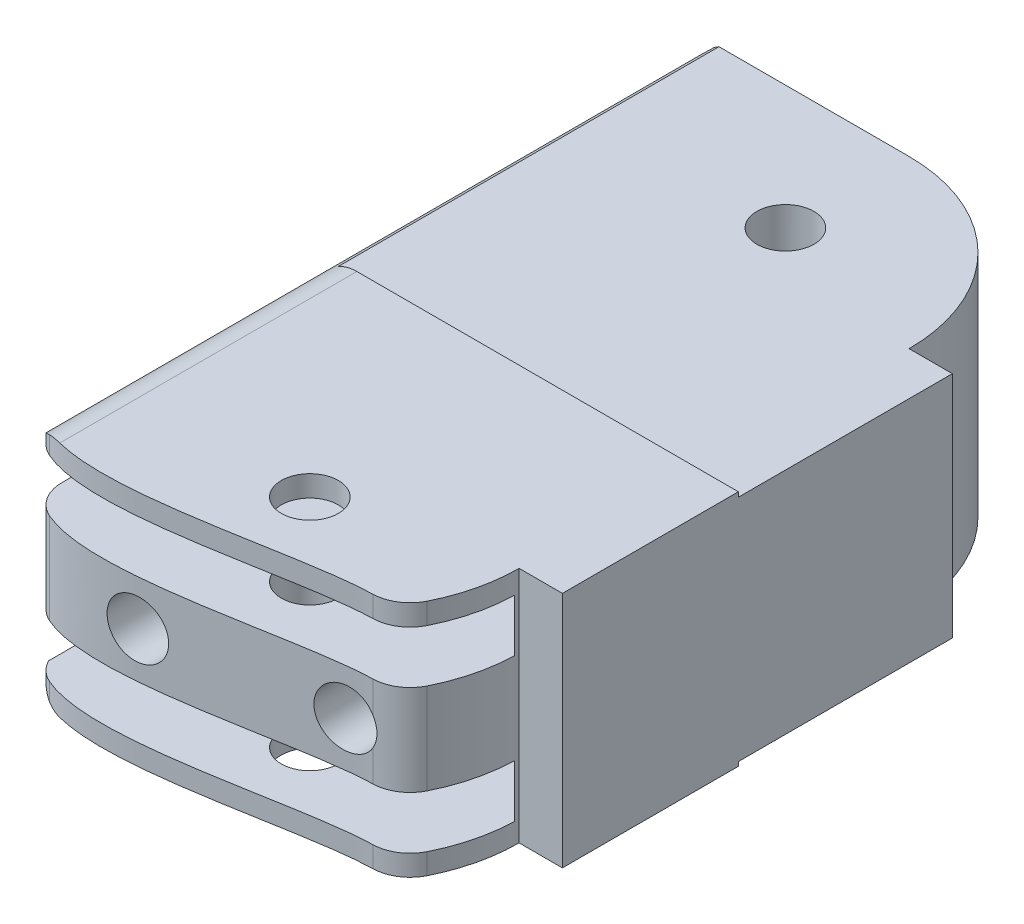
SolidWorks part; units mm, degrees
ref_plane "Front Plane" through (0, 0, 0) normal (0, 0, 1) x (1, 0, 0)
ref_plane "Top Plane" through (0, 0, 0) normal (0, 1, 0) x (1, 0, 0)
ref_plane "Right Plane" through (0, 0, 0) normal (1, 0, 0) x (0, 0, -1)
sketch "Sketch1" plane through (0, 0, 0) normal (0, 0, 1) x (1, 0, 0)
  line L0 (-24.2561, -24.0702) -> (-22.0061, -24.0702) construction
  line L1 (-24.2561, -17.8202) -> (-2.2017, -17.8202)
  line L2 (-24.2561, -17.8202) -> (-24.2561, -30.3202)
  line L3 (-24.2561, -30.3202) -> (-2.2017, -30.3202)
  line L4 (-2.2017, -17.8202) -> (-2.2017, -30.3202)
  line L5 (-2.2017, -24.0702) -> (-4.4517, -24.0702) construction
  line L6 (-22.0061, -24.0702) -> (-22.0061, -30.3202) construction
  line L7 (-4.4517, -24.0702) -> (-4.4517, -30.3202) construction
extrude "Boss-Extrude1" add sketch "Sketch1" along normal blind 38
sketch "Sketch2" plane through (0, -30.3202, 0) normal (0, -1, 0) x (1, 0, 0)
  line L0 (-4.4789, 29.25) -> (-2.2017, 29.25)
  line L1 (-24.2561, 0) -> (-2.2017, 0) construction
  line L2 (-13.2289, 0) -> (-13.2289, 8.75) construction
  line L4 (-24.2561, 38) -> (-24.2561, 0) construction
  line L5 (-4.4789, 8.75) -> (-2.2017, 8.75)
  line L6 (-2.2017, 38) -> (-2.2017, 0) construction
  line L7 (-13.2289, 38) -> (-13.2289, 29.25) construction
  line L8 (-24.2561, 38) -> (-2.2017, 38) construction
  line L10 (-13.2289, 29.25) -> (-13.2289, 31.5) construction
  line L11 (-13.2289, 8.75) -> (-13.2289, 6.5) construction
  line L12 (-24.2561, 0) -> (-2.2017, 0) construction
  arc A1 (-13.2289, 0) -> (-4.4789, 8.75) centre (-13.2289, 8.75) ccw
  circle A4 centre (-13.2289, 6.5) radius 1.5
  circle A5 centre (-13.2289, 31.5) radius 1.5
  arc A6 (-4.4789, 29.25) -> (-6.1039, 34.329) centre (-13.2289, 29.25) ccw
  spline S0 degree 3 poles (-2.2017, 8.75) (5.3921, 3.8803) (-0.7771, -4.5233) (-17.1743, -10.6233) (-34.8214, -0.026) (-24.2561, 8.75) knots 0 0 0 0 0.283273 0.504245 1 1 1 1
  spline S1 degree 3 poles (-24.2561, 29.25) (-34.2779, 38.4171) (-13.2275, 50.308) (7.8404, 38.417) (-2.2017, 29.25) knots 0 0 0 0 0.499862 1 1 1 1
  spline S2 degree 1 poles (-13.2289, 0) (-23.4906, 0) knots 0 0 1 1
  spline S3 degree 2 poles (-23.4906, 0) (-24.9665, 4.2378) (-24.2561, 8.75) knots 0 0 0 1 1 1
  spline S4 degree 3 poles (-6.1039, 34.329) (-10.7206, 33.5272) (-28.6414, 40.8452) (-24.2561, 29.25) knots 0 0 0 0 1 1 1 1
extrude "Cut-Extrude1" cut sketch "Sketch2" against normal blind 15 and the other way blind 10
fillet "Fillet3" radius 2 4 edges at (-24.2561, -17.8202, 18.7439) (-24.2561, -30.3202, 18.7439) (-24.2561, -24.0702, 3.0015) (-24.2561, -24.0702, 34.4864)
ref_plane "Plane1" through (0, 0, 0) normal (0, 0, 1) x (1, 0, 0)
sketch "Sketch5" plane through (0, 0, 0) normal (0, 0, 1) x (1, 0, 0)
  line L0 (-2.2017, -24.0702) -> (-8.4468, -24.0702) construction
  line L1 (-2.2017, -30.3202) -> (-24.2561, -30.3202) construction
  line L2 (-2.2017, -30.3202) -> (-2.2017, -17.8202) construction
  line L3 (-2.2017, -17.8202) -> (-24.2561, -17.8202) construction
  line L4 (-24.2561, -30.3202) -> (-24.2561, -17.8202) construction
  line L5 (-24.2561, -24.0702) -> (-18.0111, -24.0702) construction
  circle A0 centre (-18.0111, -24.0702) radius 1.5
  circle A1 centre (-8.4468, -24.0702) radius 1.5
extrude "Cut-Extrude4" cut sketch "Sketch5" along normal through all
ref_plane "Plane5" through (0, 0, 38) normal (0, 0, 1) x (1, 0, 0)
sketch "Sketch16" plane through (0, 0, 38) normal (0, 0, 1) x (1, 0, 0)
  line L0 (-2.2017, -17.681) -> (-2.2017, -18.9317) construction
  line L1 (-2.2017, -17.681) -> (-24.2561, -17.681) construction
  line L3 (-2.2017, -30.7619) -> (-24.2561, -30.7619) construction
  line L5 (-2.2017, -17.681) -> (-24.2561, -30.7619) construction
  line L6 (-2.2017, -30.7619) -> (-24.2561, -17.681) construction
  line L7 (-8.4468, -24.0702) -> (-8.4468, -26.4594) construction
  line L8 (-8.4468, -24.0702) -> (-8.4468, -21.681) construction
  line L9 (-2.2017, -18.9317) -> (-24.2561, -18.9317)
  line L10 (-2.2017, -18.9317) -> (-2.2017, -21.681)
  line L11 (-2.2017, -21.681) -> (-24.2561, -21.681)
  line L12 (-24.2561, -18.9317) -> (-24.2561, -21.681)
  line L13 (-2.2017, -18.9317) -> (-24.2561, -21.681) construction
  line L14 (-2.2017, -21.681) -> (-24.2561, -18.9317) construction
  line L15 (-2.1129, -29.2246) -> (-24.2561, -29.2246)
  line L16 (-2.1129, -29.2246) -> (-2.1129, -26.4594)
  line L17 (-2.1129, -26.4594) -> (-24.2561, -26.4594)
  line L18 (-24.2561, -29.2246) -> (-24.2561, -26.4594)
  line L19 (-2.1129, -29.2246) -> (-24.2561, -26.4594) construction
  line L20 (-2.1129, -26.4594) -> (-24.2561, -29.2246) construction
  point P4 (-13.2289, -24.2214)
  point P10 (-13.2289, -20.3063)
  point P14 (-13.1845, -27.842)
extrude "Cut-Extrude6" cut sketch "Sketch16" against normal blind 8.5
fillet "Fillet4" radius 2 3 edges at (-6.1039, -18.3759, 34.329) (-6.1039, -24.0702, 34.329) (-6.1039, -29.7724, 34.329)
sketch "Sketch17" plane through (0, 0, 29.5) normal (0, 0, 1) x (1, 0, 0)
  line L0 (-24.2561, -21.681) -> (-4.4825, -21.681) construction
  line L1 (-4.4825, -18.9317) -> (-23.0301, -18.9317)
  line L2 (-4.4825, -18.9317) -> (-4.4825, -21.681)
  line L3 (-4.4825, -21.681) -> (-23.0301, -21.681)
  line L4 (-23.0301, -18.9317) -> (-23.0301, -21.681)
  line L5 (-4.4825, -18.9317) -> (-23.0301, -21.681) construction
  line L6 (-4.4825, -21.681) -> (-23.0301, -18.9317) construction
  line L7 (-24.04, -29.2246) -> (-4.4825, -29.2246) construction
  line L8 (-4.4825, -26.4594) -> (-23.0301, -26.4594)
  line L9 (-4.4825, -26.4594) -> (-4.4825, -29.2246)
  line L10 (-4.4825, -29.2246) -> (-23.0301, -29.2246)
  line L11 (-23.0301, -26.4594) -> (-23.0301, -29.2246)
  line L12 (-4.4825, -26.4594) -> (-23.0301, -29.2246) construction
  line L13 (-4.4825, -29.2246) -> (-23.0301, -26.4594) construction
  point P4 (-13.7563, -20.3063)
  point P12 (-13.7563, -27.842)
extrude "Cut-Extrude7" cut sketch "Sketch17" against normal blind 5
sketch "Sketch18" plane through (0, 0, 0) normal (0, 0, 1) x (1, 0, 0)
  line L1 (-1.9195, -30.846) -> (-25.7995, -30.846)
  line L2 (-1.9195, -30.846) -> (-1.9195, -30.1039)
  line L3 (-1.9195, -30.1039) -> (-25.7995, -30.1039)
  line L4 (-25.7995, -30.846) -> (-25.7995, -30.1039)
  line L5 (-1.9195, -30.846) -> (-25.7995, -30.1039) construction
  line L6 (-1.9195, -30.1039) -> (-25.7995, -30.846) construction
  line L7 (-1.8175, -18.0686) -> (-25.7995, -18.0686)
  line L8 (-1.8175, -18.0686) -> (-1.8175, -17.3618)
  line L9 (-1.8175, -17.3618) -> (-25.7995, -17.3618)
  line L10 (-25.7995, -18.0686) -> (-25.7995, -17.3618)
  line L11 (-1.8175, -18.0686) -> (-25.7995, -17.3618) construction
  line L12 (-1.8175, -17.3618) -> (-25.7995, -18.0686) construction
  point P4 (-13.8595, -30.4749)
  point P9 (-13.8085, -17.7152)
  point P10 (-1.9329, -30.1683)
  point P11 (-1.8175, -18.0686)
  point P12 (-1.9195, -30.1039)
extrude "Cut-Extrude8" cut sketch "Sketch18" along normal blind 20
